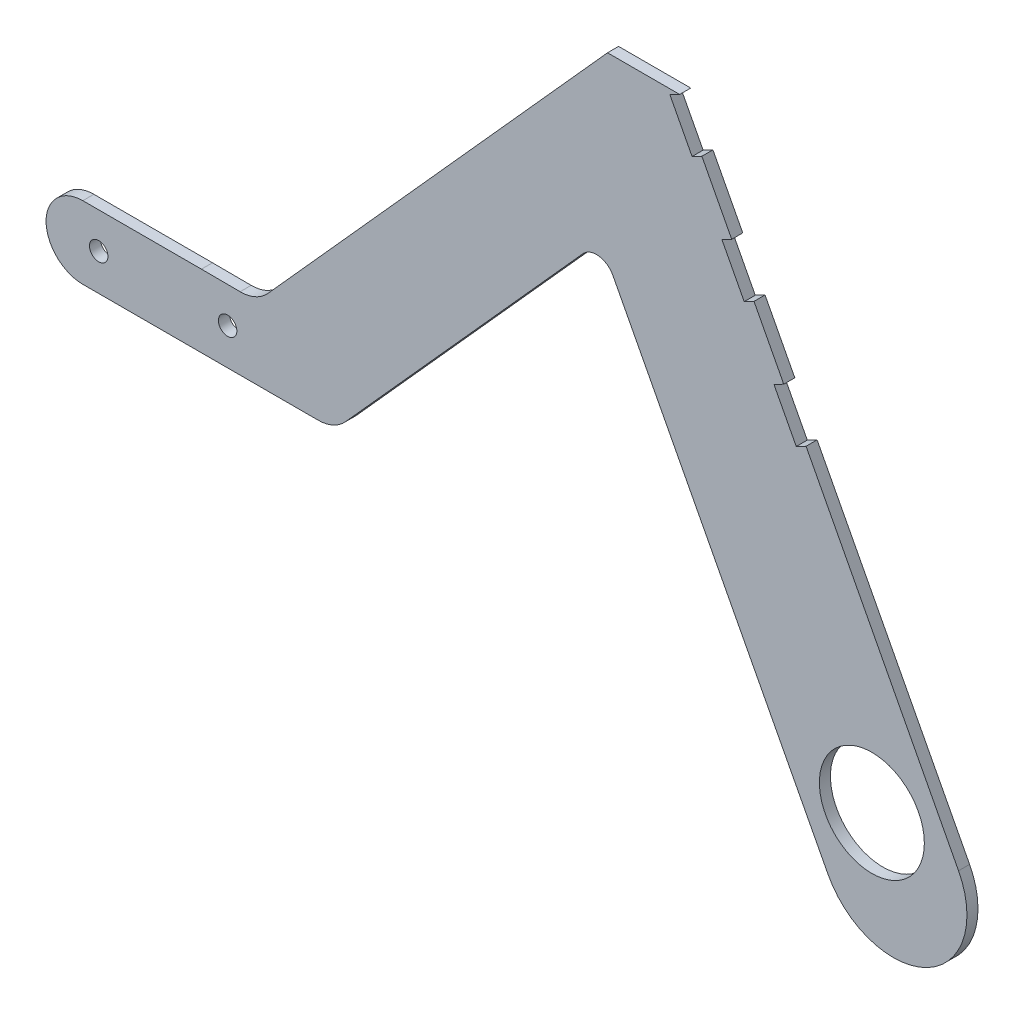
SolidWorks part; units mm, degrees
ref_plane "Front Plane" through (0, 0, 0) normal (0, 0, 1) x (1, 0, 0)
ref_plane "Top Plane" through (0, 0, 0) normal (0, 1, 0) x (1, 0, 0)
ref_plane "Right Plane" through (0, 0, 0) normal (1, 0, 0) x (0, 0, -1)
sketch "Croquis1" plane through (0, 0, 0) normal (0, 0, 1) x (1, 0, 0)
  line L0 (-135.8112, 31.6609) -> (-65.8732, 31.6609)
  line L1 (-62.1542, 33.3189) -> (39.3775, 146.3066)
  line L2 (47.5265, 145.283) -> (132.6354, -17.3455)
  line L3 (97.1952, -35.8925) -> (38.7881, 75.7135)
  line L4 (30.639, 76.7371) -> (-44.3213, -6.6811)
  line L5 (-48.0403, -8.3391) -> (-135.8112, -8.3391)
  arc A0 (132.6354, -17.3455) -> (97.1952, -35.8925) centre (114.9153, -26.619) cw
  arc A1 (-135.8112, -8.3391) -> (-135.8112, 31.6609) centre (-135.8112, 11.6609) cw
  circle A3 centre (-135.8112, 11.6609) radius 2.5
  circle A4 centre (-65.8112, 11.5885) radius 2.5
  circle A6 centre (109.0986, -15.5043) radius 14.25
  arc A7 (-62.1542, 33.3189) -> (-65.8732, 31.6609) centre (-65.8732, 36.6609) cw
  arc A8 (47.5265, 145.283) -> (39.3775, 146.3066) centre (43.0965, 142.9647) ccw
  arc A9 (38.7881, 75.7135) -> (30.639, 76.7371) centre (34.3581, 73.3952) ccw
  arc A10 (-44.3213, -6.6811) -> (-48.0403, -8.3391) centre (-48.0403, -3.3391) cw
  point P17 (-155.8112, 11.6609)
  point P18 (124.1888, -44.3391)
  point P22 (44.1888, 151.6609)
  point P27 (-45.8112, -8.3391)
  dimension "D10" = 5
  dimension "D11" = 28.5
  dimension "D13" = 5
  dimension "D1" = 40
  dimension "D2" = 40
  dimension "D3" = 40
  dimension "D4" = 70
  dimension "D5" = 90
  dimension "D6" = 280
  dimension "D7" = 56
  dimension "D8" = 90
  dimension "D9" = 120
  dimension "D12" = 20
extrude "Saliente-Extruir1" add sketch "Croquis1" along normal blind 3
sketch "Croquis3" plane through (96.9936, 50.7599, 0) normal (0.886, 0.4637, 0) x (0, 0, -1)
  line L0 (-3, -76.868) -> (-3, 106.6846) construction
  line L1 (-3, 86.4289) -> (0, 86.4289)
  line L2 (-3, 86.4289) -> (-3, 73.4264)
  line L3 (-3, 73.4264) -> (0, 73.4264)
  line L4 (0, 86.4289) -> (0, 73.4264)
  line L5 (0, 86.4289) -> (-3, 86.4289) construction
  line L6 (0, -76.868) -> (0, 106.6846) construction
  line L7 (0, 55.953) -> (-3, 55.953) construction
  line L8 (-3, 55.953) -> (0, 55.953)
  line L9 (-3, 55.953) -> (-3, 42.9048)
  line L10 (-3, 42.9048) -> (0, 42.9048)
  line L11 (0, 55.953) -> (0, 42.9048)
  line L12 (0, 42.9048) -> (-3, 42.9048) construction
  line L13 (0, 25.4771) -> (-3, 25.4771) construction
  line L14 (-3, 25.4771) -> (0, 25.4771)
  line L15 (-3, 25.4771) -> (-3, 12.4289)
  line L16 (-3, 12.4289) -> (0, 12.4289)
  line L17 (0, 25.4771) -> (0, 12.4289)
  line L18 (0, 12.4289) -> (-3, 12.4289) construction
extrude "Cortar-Extruir1" cut sketch "Croquis3" against normal blind 3
sketch "Croquis4" plane through (0, 0, 3) normal (0, 0, 1) x (1, 0, 0)
  line L1 (-177.2002, -8.3391) -> (-13.5247, -8.3391)
  line L2 (-177.2002, -8.3391) -> (-177.2002, 1.6609)
  line L3 (-177.2002, 1.6609) -> (-13.5247, 1.6609)
  line L4 (-13.5247, -8.3391) -> (-13.5247, 1.6609)
  dimension "D1" = 10
extrude "Cortar-Extruir2" cut sketch "Croquis4" against normal blind 10
fillet "Redondeo1" radius 10 2 edges at (-36.8251, 1.6609, 1.5) (-153.1317, 1.6609, 1.5)
sketch "Croquis5" plane through (0, 0, 3) normal (0, 0, 1) x (1, 0, 0)
  line L0 (-110.8112, 21.5309) -> (-110.8112, 1.7392)
  line L1 (109.0986, -15.5043) -> (109.0986, 11.5885) construction
  line L2 (109.0986, 11.5885) -> (-65.8112, 11.5885) construction
  line L3 (43.7197, 147.9257) -> (43.7197, 11.5885) construction
  line L4 (34.9812, 78.3562) -> (34.9812, 11.5885) construction
  line L5 (56.9186, 127.3363) -> (22.3306, 127.3363) construction
  line L6 (39.3775, 146.3066) -> (-62.1542, 33.3189) construction
  line L7 (-33.8452, 4.9769) -> (30.639, 76.7371) construction
  line L8 (38.7881, 75.7135) -> (97.1952, -35.8925) construction
  line L9 (-135.8112, 1.6609) -> (-135.8112, 21.6609) construction
  line L10 (-110.8112, 21.5309) -> (-72.9241, 21.3338)
  line L11 (-135.8112, 1.6609) -> (-41.2833, 1.6609) construction
  line L12 (-54.8896, 41.4031) -> (-72.9241, 21.3338) construction
  line L13 (37.3306, 127.3363) -> (-57.9243, 21.2558)
  line L14 (37.3306, 127.3363) -> (22.3306, 127.3363)
  line L15 (22.3306, 127.3363) -> (-72.9241, 21.3338)
  line L16 (-72.9241, 21.3338) -> (-57.9243, 21.2558)
  line L20 (-110.8112, 1.7392) -> (-173.4487, 1.7392)
  line L21 (-173.4487, 1.7392) -> (-173.4487, 31.6609)
  line L22 (-173.4487, 31.6609) -> (-48.5811, 31.6609)
  circle A0 centre (-135.8112, 11.6609) radius 1.58
  circle A1 centre (109.0986, -15.5043) radius 14.25
  arc A2 (47.5265, 145.283) -> (39.3775, 146.3066) centre (43.0965, 142.9647) ccw construction
  arc A3 (38.7881, 75.7135) -> (30.639, 76.7371) centre (34.3581, 73.3952) ccw construction
  arc A4 (97.1952, -35.8925) -> (132.6354, -17.3455) centre (114.9153, -26.619) ccw construction
  circle A5 centre (-100.8112, 11.6247) radius 2.5
  point P25 (-27.904, 11.5885)
  point P26 (72.3468, 11.5885)
  point P29 (96.829, -35.1563)
  point P32 (130.5843, -14.19)
  point P36 (86.264, -15.0049)
  point P37 (97.1952, -35.8925)
  point P41 (-135.8112, 11.6609)
  point P44 (37.3306, 127.3363)
  point P45 (-57.9243, 21.2558)
  point P47 (10.09, 113.7146)
  line M26 (39.3775, 146.3066) -> (-62.1542, 33.3189)
  dimension "D1" = 3.16
  dimension "D2" = 28.5
  dimension "D9" = 5
  dimension "D3" = 21.5259
  dimension "D4" = 22.8401
  dimension "D5" = 23.1678
  dimension "D6" = 10
  dimension "D7" = 15
  dimension "D8" = 15
extrude "Cortar-Extruir3" cut sketch "Croquis5" against normal blind 10 contours L22 L15 L16 L13 | L15 L22 L13 L14 M26 | A5 region at (-60.7593, 26.4774, 3) region at (-13.171, 79.4652, 3)
sketch "Croquis6" plane through (0, 0, 3) normal (0, 0, 1) x (1, 0, 0)
  line L0 (-72.9241, 21.3338) -> (-60.7137, 34.9219)
  line L1 (-60.7137, 34.9219) -> (-169.535, 34.9219)
  line L2 (-169.535, 34.9219) -> (-169.535, 0)
  line L3 (-169.535, 0) -> (-115.1243, 0)
  line L4 (-115.1243, 0) -> (-115.1243, 21.3338)
  line L5 (-115.1243, 21.3338) -> (-72.9241, 21.3338)
extrude "Cortar-Extruir4" cut sketch "Croquis6" against normal blind 10
sketch "Croquis7" plane through (0, 0, 3) normal (0, 0, 1) x (1, 0, 0)
  line L0 (22.3306, 127.3363) -> (78.8394, 127.3363)
  line L1 (78.8394, 127.3363) -> (43.1638, 161.799)
  line L2 (43.1638, 161.799) -> (22.3306, 127.3363)
extrude "Cortar-Extruir5" cut sketch "Croquis7" against normal blind 10
fillet "Redondeo2" radius 10 3 edges at (-57.9243, 21.2558, 1.5) (-115.1243, 1.6609, 1.5) (-115.1243, 21.3338, 1.5)
